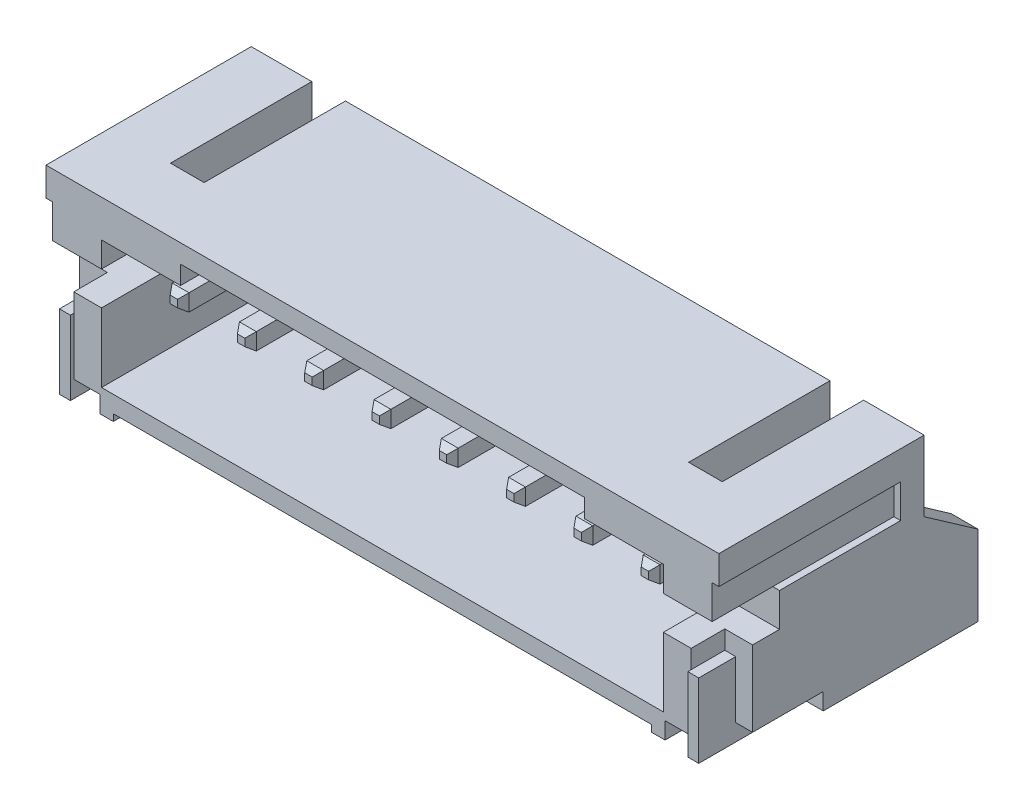
SolidWorks part; units mm, degrees
ref_plane "Спереди" through (0, 0, 0) normal (0, 0, 1) x (1, 0, 0)
ref_plane "Сверху" through (0, 0, 0) normal (0, 1, 0) x (1, 0, 0)
ref_plane "Справа" through (0, 0, 0) normal (1, 0, 0) x (0, 0, -1)
sketch "Эскиз1" plane through (0, 0, 0) normal (0, 0, 1) x (1, 0, 0)
  line L0 (0, 2.1606) -> (0, -3.4394) construction
  line L1 (-10, 2.1606) -> (10, 2.1606)
  line L2 (-10, 2.1606) -> (-10, -3.4394)
  line L3 (-10, -3.4394) -> (10, -3.4394)
  line L4 (10, 2.1606) -> (10, -3.4394)
  line L5 (-6, 1.6106) -> (6, 1.6106)
  line L6 (-8.35, 1.0606) -> (-6, 1.0606)
  line L7 (-8.35, 1.0606) -> (-8.35, -2.7394)
  line L8 (-8.35, -2.7394) -> (8.35, -2.7394)
  line L9 (8.35, 1.0606) -> (8.35, -2.7394)
  line L10 (-8.35, 1.0606) -> (8.35, -2.7394) construction
  line L11 (-8.35, -2.7394) -> (8.35, 1.0606) construction
  line L12 (-6, 1.6106) -> (-6, 1.0606)
  line L13 (6, 1.6106) -> (6, 1.0606)
  line L14 (6, 1.0606) -> (8.35, 1.0606)
  point P0 (0, 0)
  point P8 (0, -0.8394)
  point P16 (0, 1.6106)
  dimension "D1" = 20
  dimension "D2" = 5.6
  dimension "D3" = 16.7
  dimension "D4" = 0.7
  dimension "D5" = 3.8
  dimension "D6" = 12
  dimension "D7" = 0.55
extrude "Бобышка-Вытянуть1" add sketch "Эскиз1" along normal blind 4.8
sketch "Эскиз2" plane through (0, 0, 0) normal (0, 0, -1) x (-1, 0, 0)
  line L1 (-10, 2.1606) -> (10, 2.1606)
  line L2 (-10, 2.1606) -> (-10, -3.4394)
  line L3 (-10, -3.4394) -> (10, -3.4394)
  line L4 (10, 2.1606) -> (10, -3.4394)
extrude "Бобышка-Вытянуть2" add sketch "Эскиз2" along normal blind 1.3
sketch "Эскиз3" plane through (0, 0, -1.3) normal (0, 0, -1) x (-1, 0, 0)
  line L0 (-10, -3.4394) -> (10, -3.4394) construction
  line L5 (0.75, 0) -> (1.25, 0)
  line L37 (0.75, 0) -> (0.75, -3.4394)
  line L38 (0.75, -3.4394) -> (1.25, -3.4394)
  line L53 (1.25, 0) -> (1.25, -3.4394)
  line L56 (2.75, 0) -> (2.75, -3.4394)
  line L57 (2.75, 0) -> (3.25, 0)
  line L58 (3.25, 0) -> (3.25, -3.4394)
  line L59 (2.75, -3.4394) -> (3.25, -3.4394)
  line L60 (4.75, 0) -> (4.75, -3.4394)
  line L61 (4.75, 0) -> (5.25, 0)
  line L62 (5.25, 0) -> (5.25, -3.4394)
  line L63 (4.75, -3.4394) -> (5.25, -3.4394)
  line L64 (6.75, 0) -> (6.75, -3.4394)
  line L65 (6.75, 0) -> (7.25, 0)
  line L66 (7.25, 0) -> (7.25, -3.4394)
  line L67 (6.75, -3.4394) -> (7.25, -3.4394)
  line L68 (0, 0) -> (0, -3.4394) construction
  line L69 (-6.75, -3.4394) -> (-7.25, -3.4394)
  line L70 (-7.25, 0) -> (-7.25, -3.4394)
  line L71 (-6.75, 0) -> (-7.25, 0)
  line L72 (-6.75, 0) -> (-6.75, -3.4394)
  line L73 (-4.75, -3.4394) -> (-5.25, -3.4394)
  line L74 (-5.25, 0) -> (-5.25, -3.4394)
  line L75 (-4.75, 0) -> (-5.25, 0)
  line L76 (-4.75, 0) -> (-4.75, -3.4394)
  line L77 (-2.75, -3.4394) -> (-3.25, -3.4394)
  line L78 (-3.25, 0) -> (-3.25, -3.4394)
  line L79 (-2.75, 0) -> (-3.25, 0)
  line L80 (-2.75, 0) -> (-2.75, -3.4394)
  line L81 (-1.25, 0) -> (-1.25, -3.4394)
  line L82 (-0.75, -3.4394) -> (-1.25, -3.4394)
  line L83 (-0.75, 0) -> (-0.75, -3.4394)
  line L84 (-0.75, 0) -> (-1.25, 0)
  point P6 (1, 0)
  point P43 (-1, 0)
  dimension "D1" = 0.5
  dimension "D2" = 1
extrude "Бобышка-Вытянуть3" add sketch "Эскиз3" along normal blind 0.5
sketch "Эскиз4" plane through (0, 0, -1.8) normal (0, 0, -1) x (-1, 0, 0)
  line L39 (-6.75, -3.4394) -> (-6.75, 0) construction
  line L40 (-7.25, -3.4394) -> (-6.75, -3.4394)
  line L41 (-7.25, -3.4394) -> (-7.25, -2.9394)
  line L42 (-7.25, -2.9394) -> (-6.75, -2.9394)
  line L43 (-6.75, -3.4394) -> (-6.75, -2.9394)
  line L44 (-5.25, -3.4394) -> (-5.25, -2.9394)
  line L45 (-5.25, -3.4394) -> (-4.75, -3.4394)
  line L46 (-4.75, -3.4394) -> (-4.75, -2.9394)
  line L47 (-5.25, -2.9394) -> (-4.75, -2.9394)
  line L48 (-3.25, -3.4394) -> (-3.25, -2.9394)
  line L49 (-3.25, -3.4394) -> (-2.75, -3.4394)
  line L50 (-2.75, -3.4394) -> (-2.75, -2.9394)
  line L51 (-3.25, -2.9394) -> (-2.75, -2.9394)
  line L52 (-1.25, -3.4394) -> (-1.25, -2.9394)
  line L53 (-1.25, -3.4394) -> (-0.75, -3.4394)
  line L54 (-0.75, -3.4394) -> (-0.75, -2.9394)
  line L55 (-1.25, -2.9394) -> (-0.75, -2.9394)
  line L56 (0.75, -3.4394) -> (0.75, -2.9394)
  line L57 (0.75, -3.4394) -> (1.25, -3.4394)
  line L58 (1.25, -3.4394) -> (1.25, -2.9394)
  line L59 (0.75, -2.9394) -> (1.25, -2.9394)
  line L60 (2.75, -3.4394) -> (2.75, -2.9394)
  line L61 (2.75, -3.4394) -> (3.25, -3.4394)
  line L62 (3.25, -3.4394) -> (3.25, -2.9394)
  line L63 (2.75, -2.9394) -> (3.25, -2.9394)
  line L64 (4.75, -3.4394) -> (4.75, -2.9394)
  line L65 (4.75, -3.4394) -> (5.25, -3.4394)
  line L66 (5.25, -3.4394) -> (5.25, -2.9394)
  line L67 (4.75, -2.9394) -> (5.25, -2.9394)
  line L68 (6.75, -3.4394) -> (6.75, -2.9394)
  line L69 (6.75, -3.4394) -> (7.25, -3.4394)
  line L70 (7.25, -3.4394) -> (7.25, -2.9394)
  line L71 (6.75, -2.9394) -> (7.25, -2.9394)
extrude "Бобышка-Вытянуть4" add sketch "Эскиз4" along normal blind 2.2
sketch "Эскиз5" plane through (0, 0, -1.3) normal (0, 0, -1) x (-1, 0, 0)
  line L0 (0, 0) -> (0, -5.4151) construction
  line L1 (-10, -3.4394) -> (-9.2, -3.4394)
  line L2 (-10, -3.4394) -> (-10, 0.0606)
  line L3 (-10, 0.0606) -> (-9.2, 0.0606)
  line L4 (-9.2, -3.4394) -> (-9.2, 0.0606)
  line L5 (10, 0.0606) -> (9.2, 0.0606)
  line L6 (9.2, -3.4394) -> (9.2, 0.0606)
  line L7 (10, -3.4394) -> (9.2, -3.4394)
  line L8 (10, -3.4394) -> (10, 0.0606)
  dimension "D1" = 0.8
  dimension "D2" = 3.5
extrude "Бобышка-Вытянуть5" add sketch "Эскиз5" along normal blind 1.6
chamfer "Фаска1" distance 1.6 angle 35 2 edges at (-9.6, 0.0606, -2.9) (9.6, 0.0606, -2.9)
sketch "Эскиз6" plane through (0, 0, -1.3) normal (0, 0, -1) x (-1, 0, 0)
  line L0 (-9.2, -3.4394) -> (-9.2, 0.0606) construction
  line L1 (-9.2, -2.8394) -> (9.2, -2.8394)
  line L2 (-9.2, -2.8394) -> (-9.2, -0.8394)
  line L3 (-9.2, -0.8394) -> (9.2, -0.8394)
  line L4 (9.2, -2.8394) -> (9.2, -0.8394)
  line L5 (9.2, 0.0606) -> (9.2, -3.4394) construction
  line L7 (0, 0) -> (0, 2.1606) construction
  line L8 (10, 2.1606) -> (-10, 2.1606) construction
  line L10 (-1.8, 1.6106) -> (1.8, 1.6106)
  line L11 (-1.8, 1.6106) -> (-1.8, 0.6106)
  line L12 (-1.8, 0.6106) -> (1.8, 0.6106)
  line L13 (1.8, 1.6106) -> (1.8, 0.6106)
  line L14 (-1.8, 1.6106) -> (1.8, 0.6106) construction
  line L15 (-1.8, 0.6106) -> (1.8, 1.6106) construction
  point P15 (0, 1.1106)
  dimension "D2" = 2
  dimension "D3" = 3.6
  dimension "D4" = 1
  dimension "D5" = 0.55
extrude "Вырез-Вытянуть1" cut sketch "Эскиз6" against normal blind 0.8
sketch "Эскиз7" plane through (0, 0, -1.3) normal (0, 0, -1) x (-1, 0, 0)
  line L0 (10, 2.1606) -> (-10, 2.1606) construction
  line L1 (8.2, 2.1606) -> (7.2, 2.1606)
  line L2 (8.2, 2.1606) -> (8.2, 1.0606)
  line L3 (8.2, 1.0606) -> (7.2, 1.0606)
  line L4 (7.2, 2.1606) -> (7.2, 1.0606)
  line L5 (10, 0.0606) -> (10, 2.1606) construction
  line L6 (0, 0) -> (0, 3.2483) construction
  line L7 (-8.2, 1.0606) -> (-7.2, 1.0606)
  line L8 (-7.2, 2.1606) -> (-7.2, 1.0606)
  line L9 (-8.2, 2.1606) -> (-7.2, 2.1606)
  line L10 (-8.2, 2.1606) -> (-8.2, 1.0606)
  dimension "D1" = 1.8
  dimension "D2" = 1
  dimension "D3" = 1.1
extrude "Вырез-Вытянуть2" cut sketch "Эскиз7" against normal blind 4.2
sketch "Эскиз8" plane through (0, 0, 4.8) normal (0, 0, 1) x (1, 0, 0)
  line L0 (10, -3.4394) -> (10, 2.1606) construction
  line L1 (10, 1.3106) -> (9.8, 1.3106)
  line L2 (10, 1.3106) -> (10, 0.3106)
  line L4 (9.8, 1.3106) -> (9.8, 0.3106)
  line L5 (10, 2.1606) -> (-10, 2.1606) construction
  line L6 (0, 0) -> (0, -3.4394) construction
  line L7 (-10, -3.4394) -> (10, -3.4394) construction
  line L17 (10, 0.3106) -> (9.8, 0.3106)
  line L18 (-10, 0.3106) -> (-9.8, 0.3106)
  line L19 (-9.8, 1.3106) -> (-9.8, 0.3106)
  line L20 (-10, 1.3106) -> (-10, 0.3106)
  line L21 (-10, 1.3106) -> (-9.8, 1.3106)
  dimension "D1" = 0.85
  dimension "D2" = 0.2
  dimension "D3" = 1
extrude "Вырез-Вытянуть3" cut sketch "Эскиз8" against normal blind 5.4
sketch "Эскиз9" plane through (0, 0, 4.8) normal (0, 0, 1) x (1, 0, 0)
  line L0 (-8.35, 1.0606) -> (-8.35, -2.7394) construction
  line L1 (-10, 0.3106) -> (-8.35, 0.3106)
  line L2 (-10, 0.3106) -> (-10, -0.6894)
  line L3 (-10, -0.6894) -> (-8.35, -0.6894)
  line L4 (-8.35, 0.3106) -> (-8.35, -0.6894)
  line L5 (8.35, -2.7394) -> (8.35, 1.0606) construction
  line L6 (10, 0.3106) -> (8.35, 0.3106)
  line L7 (10, 0.3106) -> (10, -0.6894)
  line L8 (10, -0.6894) -> (8.35, -0.6894)
  line L9 (8.35, 0.3106) -> (8.35, -0.6894)
  line L12 (-10, 0.3106) -> (-10, -3.4394) construction
  line L13 (10, -3.4394) -> (10, 0.3106) construction
extrude "Вырез-Вытянуть4" cut sketch "Эскиз9" against normal blind 1.8
sketch "Эскиз10" plane through (0, 0, 4.8) normal (0, 0, 1) x (1, 0, 0)
  line L0 (-10, -3.4394) -> (10, -3.4394) construction
  line L1 (-10, -0.6894) -> (-9.175, -0.6894)
  line L2 (-10, -0.6894) -> (-10, -3.4394)
  line L3 (-10, -3.4394) -> (-9.2, -3.4394)
  line L4 (-9.175, -0.6894) -> (-9.175, -2.9394)
  line L5 (0, 0) -> (0, -2.7394) construction
  line L6 (-9.2, -3.4394) -> (-8.4, -3.4394)
  line L8 (-9.175, -2.9394) -> (-8.4, -2.9394)
  line L9 (-8.4, -3.4394) -> (-8.4, -2.9394)
  line L10 (-8.35, -2.7394) -> (8.35, -2.7394) construction
  line L11 (10, -0.6894) -> (10, -3.4394)
  line L12 (10, -0.6894) -> (9.175, -0.6894)
  line L13 (9.175, -0.6894) -> (9.175, -2.9394)
  line L14 (9.175, -2.9394) -> (8.4, -2.9394)
  line L15 (8.4, -3.4394) -> (8.4, -2.9394)
  line L16 (9.2, -3.4394) -> (8.4, -3.4394)
  line L17 (10, -3.4394) -> (9.2, -3.4394)
  line L18 (-10, -0.6894) -> (-8.35, -0.6894) construction
  line L20 (-10, -0.6894) -> (-10, -3.4394) construction
  dimension "D1" = 0.8
  dimension "D2" = 0.5
  dimension "D3" = 0.8
extrude "Вырез-Вытянуть5" cut sketch "Эскиз10" against normal blind 1
sketch "Эскиз11" plane through (0, 0, 3.8) normal (0, 0, 1) x (1, 0, 0)
  line L0 (0, 0) -> (0, -3.4394) construction
  line L1 (-10, -3.4394) -> (-9.5, -3.4394)
  line L2 (-10, -3.4394) -> (-10, -2.9394)
  line L3 (-10, -2.9394) -> (-9.5, -2.9394)
  line L4 (-9.5, -3.4394) -> (-9.5, -2.9394)
  line L5 (-8.4, -3.4394) -> (8.4, -3.4394) construction
  line L11 (9.5, -3.4394) -> (9.5, -2.9394)
  line L12 (10, -2.9394) -> (9.5, -2.9394)
  line L13 (10, -3.4394) -> (10, -2.9394)
  line L14 (10, -3.4394) -> (9.5, -3.4394)
  dimension "D1" = 0.5
extrude "Вырез-Вытянуть6" cut sketch "Эскиз11" against normal blind 2.1
sketch "Эскиз12" plane through (0, 0, 3.8) normal (0, 0, 1) x (1, 0, 0)
  line L0 (-9.175, -2.9394) -> (-9.175, -0.6894) construction
  line L1 (-9.5, -3.4394) -> (-9.175, -3.4394)
  line L2 (-9.5, -3.4394) -> (-9.5, -1.2394)
  line L3 (-9.5, -1.2394) -> (-9.175, -1.2394)
  line L4 (-9.175, -3.4394) -> (-9.175, -1.2394)
  line L5 (0, 0) -> (0, -4.9421) construction
  line L6 (9.5, -1.2394) -> (9.175, -1.2394)
  line L7 (9.175, -3.4394) -> (9.175, -1.2394)
  line L8 (9.5, -3.4394) -> (9.175, -3.4394)
  line L9 (9.5, -3.4394) -> (9.5, -1.2394)
  dimension "D1" = 2.2
extrude "Бобышка-Вытянуть6" add sketch "Эскиз12" along normal blind 1.1
sketch "Эскиз13" plane through (0, -3.4394, 0) normal (0, -1, 0) x (1, 0, 0)
  line L1 (-9.175, 3.8) -> (-8.975, 3.8)
  line L2 (-9.175, 3.8) -> (-9.175, 1.7)
  line L3 (-9.175, 1.7) -> (-8.975, 1.7)
  line L4 (-8.975, 3.8) -> (-8.975, 1.7)
  line L5 (9.175, 3.8) -> (8.975, 3.8)
  line L6 (9.175, 3.8) -> (9.175, 1.7)
  line L7 (9.175, 1.7) -> (8.975, 1.7)
  line L8 (8.975, 3.8) -> (8.975, 1.7)
  dimension "D1" = 0.2
  dimension "D2" = 0.2
extrude "Вырез-Вытянуть7" cut sketch "Эскиз13" against normal blind 0.2
sketch "Эскиз14" plane through (0, 0, 0) normal (0, 0, 1) x (1, 0, 0)
  line L40 (6.75, -2.9394) -> (6.75, 0) construction
  line L41 (7.25, 0) -> (6.75, 0)
  line L42 (7.25, 0) -> (7.25, -0.5)
  line L43 (7.25, -0.5) -> (6.75, -0.5)
  line L44 (6.75, 0) -> (6.75, -0.5)
  line L45 (5.25, 0) -> (4.75, 0)
  line L46 (5.25, 0) -> (5.25, -0.5)
  line L47 (5.25, -0.5) -> (4.75, -0.5)
  line L48 (4.75, 0) -> (4.75, -0.5)
  line L49 (3.25, 0) -> (2.75, 0)
  line L50 (3.25, 0) -> (3.25, -0.5)
  line L51 (3.25, -0.5) -> (2.75, -0.5)
  line L52 (2.75, 0) -> (2.75, -0.5)
  line L53 (1.25, 0) -> (0.75, 0)
  line L54 (1.25, 0) -> (1.25, -0.5)
  line L55 (1.25, -0.5) -> (0.75, -0.5)
  line L56 (0.75, 0) -> (0.75, -0.5)
  line L57 (-0.75, 0) -> (-1.25, 0)
  line L58 (-0.75, 0) -> (-0.75, -0.5)
  line L59 (-0.75, -0.5) -> (-1.25, -0.5)
  line L60 (-1.25, 0) -> (-1.25, -0.5)
  line L61 (-2.75, 0) -> (-3.25, 0)
  line L62 (-2.75, 0) -> (-2.75, -0.5)
  line L63 (-2.75, -0.5) -> (-3.25, -0.5)
  line L64 (-3.25, 0) -> (-3.25, -0.5)
  line L65 (-4.75, 0) -> (-5.25, 0)
  line L66 (-4.75, 0) -> (-4.75, -0.5)
  line L67 (-4.75, -0.5) -> (-5.25, -0.5)
  line L68 (-5.25, 0) -> (-5.25, -0.5)
  line L69 (-6.75, 0) -> (-7.25, 0)
  line L70 (-6.75, 0) -> (-6.75, -0.5)
  line L71 (-6.75, -0.5) -> (-7.25, -0.5)
  line L72 (-7.25, 0) -> (-7.25, -0.5)
extrude "Бобышка-Вытянуть7" add sketch "Эскиз14" along normal blind 4
chamfer "Фаска2" distance 0.2 angle 35 64 edges at (7.25, -3.1894, -4) (7, -3.4394, -4) (6.75, -3.1894, -4) (7, -2.9394, -4) (7, -0.5, 4) (6.75, -0.25, 4) (7, 0, 4) (7.25, -0.25, 4) (-6.75, -3.1894, -4) (-7, -2.9394, -4) (-7.25, -3.1894, -4) (-7, -3.4394, -4) (-4.75, -3.1894, -4) (-5, -2.9394, -4) (-5.25, -3.1894, -4) (-5, -3.4394, -4) (-2.75, -3.1894, -4) (-3, -2.9394, -4) (-3.25, -3.1894, -4) (-3, -3.4394, -4) (-0.75, -3.1894, -4) (-1, -2.9394, -4) (-1.25, -3.1894, -4) (-1, -3.4394, -4) (1.25, -3.1894, -4) (1, -2.9394, -4) (0.75, -3.1894, -4) (1, -3.4394, -4) (3.25, -3.1894, -4) (3, -2.9394, -4) (2.75, -3.1894, -4) (3, -3.4394, -4) (5.25, -3.1894, -4) (5, -2.9394, -4) (4.75, -3.1894, -4) (5, -3.4394, -4) (-7, -0.5, 4) (-7.25, -0.25, 4) (-7, 0, 4) (-6.75, -0.25, 4) (-5, -0.5, 4) (-5.25, -0.25, 4) (-5, 0, 4) (-4.75, -0.25, 4) (-3, -0.5, 4) (-3.25, -0.25, 4) (-3, 0, 4) (-2.75, -0.25, 4) (-1, -0.5, 4) (-1.25, -0.25, 4) (-1, 0, 4) (-0.75, -0.25, 4) (1, -0.5, 4) (0.75, -0.25, 4) (1, 0, 4) (1.25, -0.25, 4) (3, -0.5, 4) (2.75, -0.25, 4) (3, 0, 4) (3.25, -0.25, 4) (5, -0.5, 4) (4.75, -0.25, 4) (5, 0, 4) (5.25, -0.25, 4)
fillet "Скругление1" radius 0.4 16 edges at (3, 0, -1.8) (1, 0, -1.8) (-1, 0, -1.8) (-3, 0, -1.8) (-5, 0, -1.8) (-7, 0, -1.8) (5, 0, -1.8) (7, 0, -1.8) (5, -2.9394, -1.8) (3, -2.9394, -1.8) (1, -2.9394, -1.8) (-1, -2.9394, -1.8) (-3, -2.9394, -1.8) (-5, -2.9394, -1.8) (-7, -2.9394, -1.8) (7, -2.9394, -1.8)
sketch "Эскиз15" plane through (0, -3.4394, 0) normal (0, -1, 0) x (1, 0, 0)
  line L0 (-8.4, 4.8) -> (8.4, 4.8) construction
  line L1 (-8, -1.3) -> (8, -1.3)
  line L2 (-8, -1.3) -> (-8, 4.8)
  line L3 (-8, 4.8) -> (8, 4.8)
  line L4 (8, -1.3) -> (8, 4.8)
  line L6 (-10, 1.7) -> (-10, -2.9) construction
  line L7 (10, 1.7) -> (10, -2.9) construction
  dimension "D1" = 2
  dimension "D2" = 2
extrude "Вырез-Вытянуть11" cut sketch "Эскиз15" against normal blind 0.2
fillet "Скругление2" radius 0.4 5 edges at (-1, -3.4394, -1.3) (1, -3.4394, -1.3) (3, -3.4394, -1.3) (5, -3.4394, -1.3) (7, -3.4394, -1.3)
